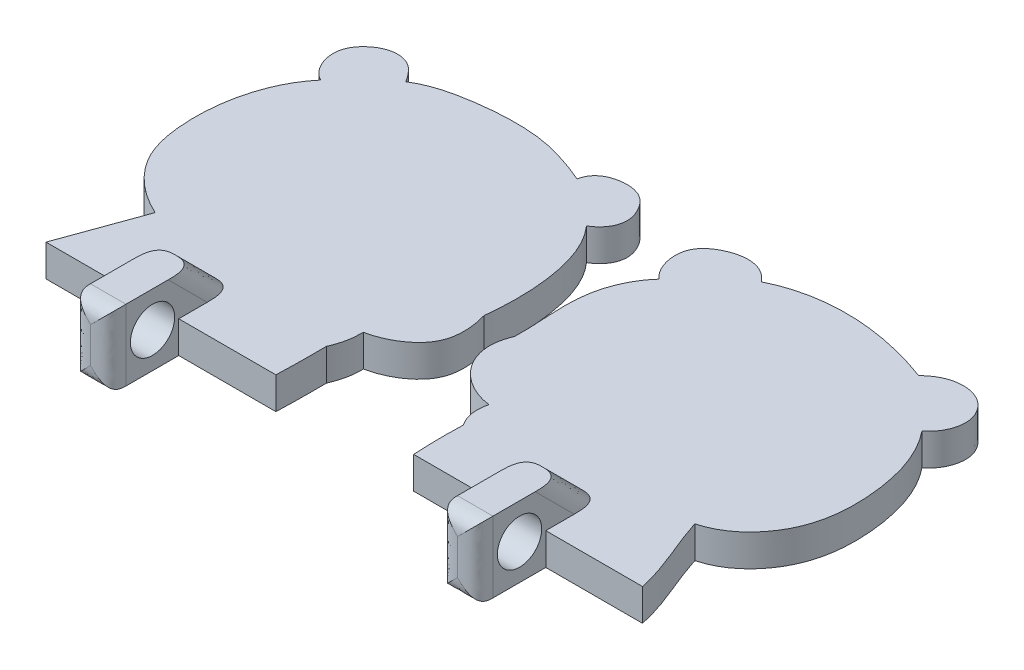
SolidWorks part; units mm, degrees
ref_plane "前视基准面" through (0, 0, 0) normal (0, 0, 1) x (1, 0, 0)
ref_plane "上视基准面" through (0, 0, 0) normal (0, 1, 0) x (1, 0, 0)
ref_plane "右视基准面" through (0, 0, 0) normal (1, 0, 0) x (0, 0, -1)
other "Configuration Table"
sketch "草图1" plane through (0, 0, 0) normal (0, 1, 0) x (1, 0, 0)
  line L0 (-15.2017, -5.0806) -> (-16.8357, -9.594)
  line L1 (-16.8357, -9.594) -> (-3.9124, -9.594)
  line L2 (3.9008, -9.594) -> (16.772, -9.594)
  arc A0 (-3.9124, -9.594) -> (-3.8798, -6.789) centre (-62.9106, -7.507) ccw
  arc A1 (3.8716, -6.7805) -> (3.9008, -9.594) centre (33.2778, -7.8816) ccw
  spline S0 degree 3 poles (-3.8798, -6.789) (-3.7551, -6.5149) (-3.6624, -6.2324) (-3.5439, -5.6496) (-3.5185, -5.3474) (-3.5264, -5.0463) knots 0 0 0 0 0.5 0.5 1 1 1 1
  spline S1 degree 3 poles (-3.5264, -5.0463) (-3.4096, -5.0216) (-3.293, -4.9962) (-3.0649, -4.9318) (-2.9527, -4.8947) (-2.6213, -4.7699) (-2.4069, -4.6691) (-1.9927, -4.4291) (-1.7979, -4.2927) (-1.4398, -3.9816) (-1.2745, -3.804) (-1.0721, -3.5109) (-1.0118, -3.4086) (-0.9084, -3.1927) (-0.8661, -3.0795) (-0.7674, -2.7366) (-0.7363, -2.4972) (-0.7177, -1.7829) (-0.8001, -1.3114) (-0.9363, -0.8529) knots 0 0 0 0 0.0625 0.0625 0.125 0.125 0.25 0.25 0.375 0.375 0.5 0.5 0.5625 0.5625 0.625 0.625 0.75 0.75 1 1 1 1
  spline S2 degree 3 poles (-0.9363, -0.8529) (-0.8688, -0.2177) (-0.831, 0.419) (-0.84, 1.6967) (-0.8861, 2.3328) (-1.0823, 3.5953) (-1.2282, 4.2135) (-1.5728, 5.0952) (-1.7089, 5.3818) (-1.9554, 5.7972) (-2.0441, 5.9322) (-2.2339, 6.1918) (-2.3373, 6.3153) (-2.4414, 6.4384) knots 0 0 0 0 0.25 0.25 0.5 0.5 0.75 0.75 0.875 0.875 0.9375 0.9375 1 1 1 1
  spline S3 degree 3 poles (-2.4414, 6.4384) (-2.3818, 6.4743) (-2.3211, 6.5091) (-2.2059, 6.5859) (-2.1512, 6.6279) (-1.9952, 6.7635) (-1.9006, 6.8682) (-1.7392, 7.0963) (-1.6726, 7.2184) (-1.5729, 7.4815) (-1.5418, 7.6177) (-1.5205, 8.0385) (-1.6007, 8.3173) (-1.8447, 8.8161) (-2.009, 9.05) (-2.3319, 9.3186) (-2.4525, 9.3916) (-2.7083, 9.498) (-2.8459, 9.5337) (-3.2581, 9.594) (-3.5421, 9.5773) (-4.0832, 9.4529) (-4.3492, 9.3391) (-4.6639, 9.061) (-4.7529, 8.9507) (-4.8514, 8.7657) (-4.8783, 8.7015) (-4.9207, 8.5686) (-4.9362, 8.4998) (-4.9536, 8.4318) knots 0 0 0 0 0.03125 0.03125 0.0625 0.0625 0.125 0.125 0.1875 0.1875 0.25 0.25 0.375 0.375 0.5 0.5 0.5625 0.5625 0.625 0.625 0.75 0.75 0.875 0.875 0.9375 0.9375 0.96875 0.96875 1 1 1 1
  spline S4 degree 3 poles (-4.9536, 8.4318) (-5.3352, 8.591) (-5.718, 8.7447) (-6.4926, 9.0136) (-6.8839, 9.1307) (-7.6784, 9.3135) (-8.0821, 9.377) (-8.9026, 9.4476) (-9.3213, 9.4565) (-10.57, 9.4267) (-11.3934, 9.3365) (-12.6165, 9.111) (-13.0245, 9.0165) (-13.7182, 8.782) (-14.006, 8.6602) (-14.3721, 8.4588) (-14.4616, 8.4041) (-14.5512, 8.3495) knots 0 0 0 0 0.125 0.125 0.25 0.25 0.375 0.375 0.5 0.5 0.75 0.75 0.875 0.875 0.96875 0.96875 1 1 1 1
  spline S5 degree 3 poles (-14.5512, 8.3495) (-14.7099, 8.5872) (-14.8725, 8.8243) (-15.1787, 9.125) (-15.289, 9.2148) (-15.5375, 9.3594) (-15.6711, 9.4089) (-16.0879, 9.4966) (-16.3857, 9.4747) (-16.789, 9.3383) (-16.9191, 9.2755) (-17.1611, 9.1263) (-17.2735, 9.0405) (-17.483, 8.8488) (-17.58, 8.7419) (-17.7458, 8.5119) (-17.8165, 8.3858) (-17.918, 8.1202) (-17.9477, 7.9825) (-17.9702, 7.6983) (-17.9627, 7.555) (-17.917, 7.2757) (-17.8782, 7.1367) (-17.7738, 6.8727) (-17.7086, 6.747) (-17.5497, 6.5092) (-17.4579, 6.4002) (-17.3011, 6.2563) (-17.2451, 6.2113) (-17.127, 6.1299) (-17.0649, 6.094) (-17.0038, 6.0565) knots 0 0 0 0 0.125 0.125 0.1875 0.1875 0.25 0.25 0.375 0.375 0.4375 0.4375 0.5 0.5 0.5625 0.5625 0.625 0.625 0.6875 0.6875 0.75 0.75 0.8125 0.8125 0.875 0.875 0.9375 0.9375 0.96875 0.96875 1 1 1 1
  spline S6 degree 3 poles (-17.0038, 6.0565) (-17.0904, 5.9511) (-17.1771, 5.8457) (-17.3396, 5.6289) (-17.4168, 5.5182) (-17.6374, 5.18) (-17.7695, 4.9461) (-18.1259, 4.2219) (-18.3111, 3.7037) (-18.5814, 2.6579) (-18.67, 2.1274) (-18.7634, 1.0528) (-18.7665, 0.5051) (-18.6882, -0.5747) (-18.6111, -1.1117) (-18.3772, -1.8972) (-18.2807, -2.15) (-18.0417, -2.6333) (-17.9, -2.8644) (-17.4154, -3.5276) (-17.0312, -3.9096) (-16.3838, -4.4125) (-16.1588, -4.5656) (-15.8092, -4.7743) (-15.6906, -4.8404) (-15.4491, -4.9655) (-15.3256, -5.0233) (-15.2017, -5.0806) knots 0 0 0 0 0.03125 0.03125 0.0625 0.0625 0.125 0.125 0.25 0.25 0.375 0.375 0.5 0.5 0.625 0.625 0.6875 0.6875 0.75 0.75 0.875 0.875 0.9375 0.9375 0.96875 0.96875 1 1 1 1
  spline S7 degree 3 poles (16.772, -9.594) (16.6107, -8.8081) (16.3306, -8.0546) (15.8849, -6.9382) (15.6553, -6.3825) (15.4419, -5.8208) (15.3061, -5.4438) (15.2428, -5.2536) (15.181, -5.0628) knots 0 0 0 0 0.5 0.5 0.75 0.875 0.875 1 1 1 1
  spline S8 degree 3 poles (15.181, -5.0628) (15.311, -5.0248) (15.4407, -4.9863) (15.6926, -4.8933) (15.8157, -4.8408) (16.1766, -4.6659) (16.4072, -4.5256) (16.8433, -4.2028) (17.044, -4.0243) (17.4149, -3.6366) (17.5859, -3.4263) (17.8941, -2.9815) (18.03, -2.7497) (18.2671, -2.2682) (18.3687, -2.0172) (18.6173, -1.2445) (18.7065, -0.7175) (18.7615, 0.0852) (18.7665, 0.356) (18.7543, 0.8938) (18.7374, 1.1608) (18.661, 1.9575) (18.5764, 2.4829) (18.3815, 3.2595) (18.3052, 3.5165) (18.1254, 4.0258) (18.0223, 4.2769) (17.7908, 4.7615) (17.5977, 5.1138) (17.373, 5.4482) (17.2159, 5.6669) (17.1324, 5.7736) (17.0487, 5.88) knots 0 0 0 0 0.03125 0.03125 0.0625 0.0625 0.125 0.125 0.1875 0.1875 0.25 0.25 0.3125 0.3125 0.375 0.375 0.5 0.5 0.5625 0.5625 0.625 0.625 0.75 0.75 0.8125 0.8125 0.875 0.875 0.9375 0.96875 0.96875 1 1 1 1
  spline S9 degree 3 poles (17.0487, 5.88) (17.1033, 5.9233) (17.1589, 5.9657) (17.2629, 6.0572) (17.312, 6.1058) (17.4511, 6.2591) (17.5339, 6.3727) (17.6748, 6.6136) (17.7324, 6.7394) (17.8225, 7.0011) (17.8552, 7.139) (17.8895, 7.4144) (17.8918, 7.5524) (17.8621, 7.829) (17.8288, 7.9671) (17.7292, 8.2254) (17.6624, 8.3496) (17.5022, 8.5785) (17.4099, 8.6824) (17.1998, 8.8684) (17.0843, 8.9473) (16.8386, 9.0765) (16.7065, 9.1277) (16.3037, 9.2372) (16.0192, 9.2535) (15.6062, 9.199) (15.4685, 9.1675) (15.2038, 9.0821) (15.076, 9.0282) (14.8295, 8.8987) (14.7108, 8.8227) (14.5456, 8.6955) (14.4925, 8.6508) (14.3902, 8.5566) (14.3416, 8.5063) (14.293, 8.4561) knots 0 0 0 0 0.03125 0.03125 0.0625 0.0625 0.125 0.125 0.1875 0.1875 0.25 0.25 0.3125 0.3125 0.375 0.375 0.4375 0.4375 0.5 0.5 0.5625 0.5625 0.625 0.625 0.75 0.75 0.8125 0.8125 0.875 0.875 0.9375 0.9375 0.96875 0.96875 1 1 1 1
  spline S10 degree 3 poles (14.293, 8.4561) (13.9286, 8.5923) (13.5617, 8.7193) (12.8193, 8.9447) (12.4443, 9.0446) (11.6861, 9.216) (11.3036, 9.2873) (10.5398, 9.3962) (10.1574, 9.4343) (9.0085, 9.4929) (8.2402, 9.4595) (7.0832, 9.2553) (6.7055, 9.1626) (6.1522, 8.9833) (5.9699, 8.9168) (5.61, 8.7697) (5.433, 8.6873) (5.257, 8.6016) knots 0 0 0 0 0.125 0.125 0.25 0.25 0.375 0.375 0.5 0.5 0.75 0.75 0.875 0.875 0.9375 0.9375 1 1 1 1
  spline S11 degree 3 poles (5.257, 8.6016) (5.2116, 8.6551) (5.1666, 8.7091) (5.0708, 8.8106) (5.0206, 8.8588) (4.8623, 8.995) (4.7449, 9.0756) (4.3711, 9.2683) (4.0899, 9.3312) (3.6698, 9.3335) (3.5281, 9.3195) (3.2535, 9.2688) (3.1192, 9.2321) (2.8554, 9.1401) (2.7251, 9.0846) (2.4762, 8.958) (2.357, 8.8866) (2.0196, 8.6411) (1.8175, 8.4313) (1.5791, 7.9174) (1.5434, 7.6303) (1.5707, 7.2118) (1.5937, 7.0716) (1.6637, 6.7993) (1.7103, 6.6674) (1.8277, 6.4122) (1.8988, 6.2888) (2.0224, 6.1201) (2.0667, 6.0662) (2.1621, 5.964) (2.2142, 5.9165) (2.2653, 5.8681) knots 0 0 0 0 0.03125 0.03125 0.0625 0.0625 0.125 0.125 0.25 0.25 0.3125 0.3125 0.375 0.375 0.4375 0.4375 0.5 0.5 0.625 0.625 0.75 0.75 0.8125 0.8125 0.875 0.875 0.9375 0.9375 0.96875 0.96875 1 1 1 1
  spline S12 degree 3 poles (2.2653, 5.8681) (2.166, 5.7544) (2.068, 5.64) (1.8882, 5.4011) (1.8044, 5.2779) (1.5697, 4.8981) (1.4357, 4.631) (1.21, 4.0709) (1.121, 3.7841) (0.9888, 3.2019) (0.9466, 2.9056) (0.8773, 2.0042) (0.905, 1.4019) (0.9707, 0.2003) (1.0084, -0.4004) (0.989, -1.0022) knots 0 0 0 0 0.0625 0.0625 0.125 0.125 0.25 0.25 0.375 0.375 0.5 0.5 0.75 0.75 1 1 1 1
  spline S13 degree 3 poles (0.989, -1.0022) (0.8977, -1.2195) (0.8273, -1.442) (0.7422, -1.901) (0.7269, -2.1394) (0.766, -2.6038) (0.8204, -2.8361) (0.9857, -3.2738) (1.0972, -3.4819) (1.3693, -3.8654) (1.5266, -4.0381) (1.8785, -4.35) (2.0705, -4.4865) (2.4756, -4.7187) (2.6922, -4.816) (3.0252, -4.927) (3.1377, -4.9583) (3.3659, -5.0091) (3.4822, -5.0264) (3.5983, -5.044) knots 0 0 0 0 0.125 0.125 0.25 0.25 0.375 0.375 0.5 0.5 0.625 0.625 0.75 0.75 0.875 0.875 0.9375 0.9375 1 1 1 1
  spline S14 degree 3 poles (3.5983, -5.044) (3.5612, -5.1916) (3.5362, -5.3403) (3.5157, -5.6406) (3.5208, -5.7942) (3.5654, -6.0927) (3.6045, -6.2373) (3.7152, -6.5176) (3.7873, -6.6534) (3.8716, -6.7805) knots 0 0 0 0 0.25 0.25 0.5 0.5 0.75 0.75 1 1 1 1
extrude "凸台-拉伸1" add sketch "草图1" along normal blind 1.8
sketch "草图2" plane through (0, 0, 9.594) normal (0, 0, 1) x (1, 0, 0)
  line L0 (-10.374, 1.8) -> (-10.374, 0) construction
  line L1 (-16.8357, 1.8) -> (-3.9124, 1.8) construction
  line L2 (-16.8357, 0) -> (-3.9124, 0) construction
  line L3 (10.3364, 1.8) -> (10.3364, 0) construction
  line L4 (3.9008, 1.8) -> (16.772, 1.8) construction
  line L5 (3.9008, 0) -> (16.772, 0) construction
  line L7 (-11.374, 4) -> (-9.374, 4)
  line L8 (-11.374, 4) -> (-11.374, 0)
  line L9 (-11.374, 0) -> (-9.374, 0)
  line L10 (-9.374, 4) -> (-9.374, 0)
  line L11 (-11.374, 4) -> (-9.374, 0) construction
  line L12 (-11.374, 0) -> (-9.374, 4) construction
  line L13 (9.3364, 4) -> (11.3364, 4)
  line L14 (9.3364, 4) -> (9.3364, 0)
  line L15 (9.3364, 0) -> (11.3364, 0)
  line L16 (11.3364, 4) -> (11.3364, 0)
  line L17 (9.3364, 4) -> (11.3364, 0) construction
  line L18 (9.3364, 0) -> (11.3364, 4) construction
  point P12 (-10.374, 2)
  point P17 (10.3364, 2)
  dimension "D1" = 2
  dimension "D2" = 2
  dimension "D3" = 4
  dimension "D4" = 4
extrude "凸台-拉伸2" add sketch "草图2" along normal blind 4
chamfer "倒角1" distance 3 angle 45 1 edges at (-10.374, 1.8, 9.594)
chamfer "倒角2" distance 3 angle 45 1 edges
fillet "圆角2" radius 1 4 edges at (-10.374, 0, 13.594) (-11.374, 2, 13.594) (-10.374, 4, 13.594) (-9.374, 2, 13.594) curvature continuous yes
fillet "圆角3" radius 1 4 edges at (10.3364, 0, 13.594) (9.3364, 2, 13.594) (10.3364, 4, 13.594) (11.3364, 2, 13.594) curvature continuous yes
sketch "草图3" plane through (11.3364, 0, 0) normal (1, 0, 0) x (0, 0, -1)
  line L0 (-13.594, 3) -> (-13.594, 1) construction
  circle A0 centre (-11.094, 2) radius 1.25
  dimension "D1" = 2.5
  dimension "D2" = 2.5
extrude "切除-拉伸1" cut sketch "草图3" against normal blind 28
fillet "圆角4" radius 1 2 edges at (-11.374, 2.9, 7.694) (-9.374, 2.9, 7.694) curvature continuous yes
fillet "圆角5" radius 1 2 edges at (11.3364, 2.9, 7.694) (9.3364, 2.9, 7.694) curvature continuous yes
sketch "草图4" plane through (0, 1.8, 0) normal (0, 1, 0) x (1, 0, 0)
  line L10 (-9.394, -8.0082) -> (-9.394, -9.614)
  line L11 (-9.394, -9.614) -> (-3.8931, -9.614)
  line L12 (-15.2268, -5.0911) -> (-16.8642, -9.614)
  line L13 (-16.8642, -9.614) -> (-11.354, -9.614)
  line L14 (-11.354, -9.614) -> (-11.354, -8.0082)
  line L15 (-9.394, -8.0082) -> (-9.394, -9.614)
  line L16 (-9.394, -9.614) -> (-3.8931, -9.614)
  line L17 (-15.2268, -5.0911) -> (-16.8642, -9.614)
  line L18 (-16.8642, -9.614) -> (-11.354, -9.614)
  line L19 (-11.354, -9.614) -> (-11.354, -8.0082)
  line L31 (9.3564, -9.614) -> (9.3564, -8.0082)
  line L32 (11.3164, -8.0082) -> (11.3164, -9.614)
  line L33 (11.3164, -9.614) -> (16.7965, -9.614)
  line L34 (3.882, -9.614) -> (9.3564, -9.614)
  line L35 (9.3564, -9.614) -> (9.3564, -8.0082)
  line L36 (11.3164, -8.0082) -> (11.3164, -9.614)
  line L37 (11.3164, -9.614) -> (16.7965, -9.614)
  line L38 (3.882, -9.614) -> (9.3564, -9.614)
  arc A2 (-3.8931, -9.614) -> (-3.8598, -6.7932) centre (-62.9106, -7.507) ccw
  arc A3 (-3.8931, -9.614) -> (-3.8598, -6.7932) centre (-62.9106, -7.507) ccw
  arc A7 (3.8513, -6.7862) -> (3.882, -9.614) centre (33.2778, -7.8816) ccw
  arc A8 (3.8513, -6.7862) -> (3.882, -9.614) centre (33.2778, -7.8816) ccw
  spline S18 degree 3 poles (-4008.6204, 131.2602) (58.4278, -31.6233) (-12.5627, -18.0279) (-11.314, -7.3478) (-11.2802, -7.1868) (-11.172, -6.9611) (-11.126, -6.8916) (-11.0086, -6.7718) (-10.94, -6.7248) (-10.7873, -6.6564) (-10.7056, -6.6392) (-1.7946, -5.4737) (12.6768, -85.8409) (-260.2207, 3985.3377) knots -15.710344 -15.710344 -15.710344 -15.710344 0.25 0.25 0.5 0.5 0.625 0.625 0.75 0.75 0.875 0.875 14.238448 14.238448 14.238448 14.238448 only from (-11.354, -8.0082) to (-10.374, -6.614)
  spline S19 degree 3 poles (349.7456, 3977.0103) (-35.796, -86.154) (-18.9879, -5.4734) (-10.0434, -6.6391) (-9.9605, -6.6566) (-9.8096, -6.724) (-9.7395, -6.7721) (-9.6235, -6.89) (-9.5766, -6.9605) (-9.5049, -7.1093) (-9.4783, -7.189) (-9.4383, -7.349) (-9.4245, -7.4301) (-8.1919, -17.9509) (-78.1632, -39.99) (3887.6311, 892.6218) knots -13.345557 -13.345557 -13.345557 -13.345557 0.125 0.125 0.25 0.25 0.375 0.375 0.5 0.5 0.625 0.625 0.75 0.75 16.684036 16.684036 16.684036 16.684036 only from (-10.374, -6.614) to (-9.394, -8.0082)
  spline S20 degree 3 poles (2048.1962, 3417.2726) (-279.9253, 4.3116) (-8.851, -31.7824) (3.7238, 29.8984) (-508.6231, 119.4535) (3508.0427, -1916.1775) knots -43.795404 -43.795404 -43.795404 -43.795404 0.5 0.5 61.956812 61.956812 61.956812 61.956812 only from (-3.8598, -6.7932) to (-3.5061, -5.0624)
  spline S21 degree 3 poles (1402.5526, -3749.3123) (-44.3506, 42.8584) (-13.4245, -7.9218) (-3.044, -4.9461) (-2.9317, -4.9085) (-2.6001, -4.7825) (-2.3858, -4.6808) (-1.9718, -4.4392) (-1.7766, -4.3016) (-1.4187, -3.9886) (-1.2536, -3.8101) (-1.0516, -3.5159) (-0.9915, -3.4131) (-0.8885, -3.1968) (-0.8462, -3.0831) (-0.7476, -2.7392) (-0.7164, -2.4994) (-0.1016, 20.792) (-220.4088, 31.6025) (3920.243, -790.6913) knots -5.55998 -5.55998 -5.55998 -5.55998 0.0625 0.0625 0.125 0.125 0.25 0.25 0.375 0.375 0.5 0.5 0.5625 0.5625 0.625 0.625 0.75 0.75 12.818632 12.818632 12.818632 12.818632 only from (-3.5061, -5.0624) to (-0.916, -0.8511)
  spline S22 degree 3 poles (3988.1598, -267.3402) (-221.4527, -84.2761) (-0.4929, -45.2055) (-0.82, 1.6941) (-0.8663, 2.3328) (-1.0116, 3.272) (-1.0718, 3.5828) (-1.2261, 4.1982) (-1.3206, 4.5039) (-1.5533, 5.1013) (-1.7583, 5.5316) (-2.0183, 5.9296) (-9.3815, 16.0894) (-71.3063, -5.9039) (3429.5649, 2059.6702) knots -17.900046 -17.900046 -17.900046 -17.900046 0.25 0.25 0.5 0.5 0.625 0.625 0.75 0.75 0.875 0.9375 0.9375 5.80626 5.80626 5.80626 5.80626 only from (-0.916, -0.8511) to (-2.411, 6.4333)
  spline S23 degree 3 poles (2580.0375, -3047.8614) (-38.8422, 30.7106) (-7.2695, 3.0777) (-2.1757, 6.5834) (-2.1214, 6.6263) (-1.9667, 6.7643) (-1.8731, 6.8702) (-1.7131, 7.1011) (-1.6475, 7.2244) (-1.5501, 7.489) (-1.5202, 7.6268) (-1.5023, 8.0484) (-1.5836, 8.3289) (-1.8294, 8.8294) (-1.9951, 9.0642) (-2.3183, 9.3335) (-2.4405, 9.4077) (-2.6975, 9.5155) (-2.8356, 9.5519) (-3.2504, 9.614) (-3.5357, 9.5982) (-4.08, 9.4752) (-4.3461, 9.364) (-4.6679, 9.0862) (-4.758, 8.9779) (-4.8611, 8.7924) (-4.8892, 8.7283) (-6.7343, 3.2877) (33.0143, -17.3237) (-3766.1994, 1369.1606) knots -2.718898 -2.718898 -2.718898 -2.718898 0.03125 0.03125 0.0625 0.0625 0.125 0.125 0.1875 0.1875 0.25 0.25 0.375 0.375 0.5 0.5 0.5625 0.5625 0.625 0.625 0.75 0.75 0.875 0.875 0.9375 0.9375 0.96875 0.96875 3.505852 3.505852 3.505852 3.505852 only from (-2.411, 6.4333) to (-4.9673, 8.4592)
  spline S24 degree 3 poles (984.5291, 3883.2745) (25.6123, -97.2483) (20.0432, -0.1362) (-6.5035, 9.0379) (-6.8942, 9.1542) (-7.6876, 9.3355) (-8.0907, 9.3983) (-8.9102, 9.4678) (-9.3284, 9.4765) (-10.5733, 9.4463) (-11.3945, 9.3564) (-12.4117, 9.1692) (-12.6145, 9.1271) (-13.0184, 9.0282) (-13.2202, 8.9711) (-13.7138, 8.8051) (-14.0008, 8.6845) (-23.1709, 3.6852) (-13.9017, -42.435) (-1653.1802, 3656.8635) knots -8.332667 -8.332667 -8.332667 -8.332667 0.125 0.125 0.25 0.25 0.375 0.375 0.5 0.5 0.75 0.75 0.8125 0.8125 0.875 0.875 0.96875 0.96875 4.010213 4.010213 4.010213 4.010213 only from (-4.9673, 8.4592) to (-14.5452, 8.3766)
  spline S25 degree 3 poles (3027.7667, 2604.9155) (-79.7425, -77.3097) (-6.026, 0.2949) (-15.1784, 9.1511) (-15.29, 9.2402) (-15.5402, 9.3823) (-15.676, 9.4313) (-16.0954, 9.5166) (-16.3944, 9.4935) (-16.7993, 9.3556) (-16.9297, 9.2926) (-17.1731, 9.1424) (-17.2859, 9.0561) (-17.6013, 8.7678) (-17.7803, 8.5332) (-17.9355, 8.1324) (-17.966, 7.9941) (-17.9902, 7.7093) (-17.9836, 7.5649) (-17.9395, 7.2841) (-17.9015, 7.1444) (-17.7986, 6.8782) (-17.734, 6.7515) (-17.5769, 6.5119) (-17.4855, 6.4009) (-17.3301, 6.2548) (-17.2751, 6.2092) (-12.2769, 2.6495) (16.3329, 35.4248) (-2201.1269, -3344.8238) knots -5.344029 -5.344029 -5.344029 -5.344029 0.125 0.125 0.1875 0.1875 0.25 0.25 0.375 0.375 0.4375 0.4375 0.5 0.5 0.625 0.625 0.6875 0.6875 0.75 0.75 0.8125 0.8125 0.875 0.875 0.9375 0.9375 0.96875 0.96875 3.595855 3.595855 3.595855 3.595855 only from (-14.5452, 8.3766) to (-17.0339, 6.0514)
  spline S26 degree 3 poles (-3489.7471, 1990.2985) (41.2907, 0.8501) (-9.9636, 15.5797) (-17.3683, 5.623) (-17.4452, 5.5121) (-17.6646, 5.1732) (-17.7961, 4.9389) (-18.1505, 4.2139) (-18.3347, 3.6954) (-18.6033, 2.65) (-18.6913, 2.1196) (-18.7836, 1.0453) (-18.7863, 0.4977) (-18.7075, -0.5813) (-18.6301, -1.118) (-18.3963, -1.9032) (-18.2998, -2.1559) (-18.0613, -2.6392) (-17.92, -2.8702) (-17.4364, -3.534) (-17.0532, -3.9165) (-16.4072, -4.4203) (-16.1824, -4.574) (-15.8334, -4.7835) (-15.715, -4.8499) (-3.8347, -11.0434) (34.4582, 27.3081) (-2030.3323, -3460.1012) knots -2.800569 -2.800569 -2.800569 -2.800569 0.03125 0.03125 0.0625 0.0625 0.125 0.125 0.25 0.25 0.375 0.375 0.5 0.5 0.625 0.625 0.6875 0.6875 0.75 0.75 0.875 0.875 0.9375 0.9375 0.96875 0.96875 4.017807 4.017807 4.017807 4.017807 only from (-17.0339, 6.0514) to (-15.2268, -5.0911)
  spline S27 degree 3 poles (-11.354, -8.0082) (-11.354, -7.8426) (-11.3525, -7.6772) (-11.314, -7.3478) (-11.2802, -7.1868) (-11.172, -6.9611) (-11.126, -6.8916) (-11.0086, -6.7718) (-10.94, -6.7248) (-10.7873, -6.6564) (-10.7056, -6.6392) (-10.5404, -6.6176) (-10.4574, -6.614) (-10.374, -6.614) knots 0 0 0 0 0.25 0.25 0.5 0.5 0.625 0.625 0.75 0.75 0.875 0.875 1 1 1 1
  spline S28 degree 3 poles (-10.374, -6.614) (-10.2908, -6.614) (-10.2078, -6.6176) (-10.0434, -6.6391) (-9.9605, -6.6566) (-9.8096, -6.724) (-9.7395, -6.7721) (-9.6235, -6.89) (-9.5766, -6.9605) (-9.5049, -7.1093) (-9.4783, -7.189) (-9.4383, -7.349) (-9.4245, -7.4301) (-9.3957, -7.6758) (-9.394, -7.8424) (-9.394, -8.0082) knots 0 0 0 0 0.125 0.125 0.25 0.25 0.375 0.375 0.5 0.5 0.625 0.625 0.75 0.75 1 1 1 1
  spline S29 degree 3 poles (-3.8598, -6.7932) (-3.7367, -6.5221) (-3.6434, -6.2384) (-3.5245, -5.6551) (-3.4994, -5.36) (-3.5061, -5.0624) knots 0 0 0 0 0.5 0.5 1 1 1 1
  spline S30 degree 3 poles (-3.5061, -5.0624) (-3.3889, -5.0376) (-3.2722, -5.0115) (-3.044, -4.9461) (-2.9317, -4.9085) (-2.6001, -4.7825) (-2.3858, -4.6808) (-1.9718, -4.4392) (-1.7766, -4.3016) (-1.4187, -3.9886) (-1.2536, -3.8101) (-1.0516, -3.5159) (-0.9915, -3.4131) (-0.8885, -3.1968) (-0.8462, -3.0831) (-0.7476, -2.7392) (-0.7164, -2.4994) (-0.6975, -1.7831) (-0.7797, -1.3108) (-0.916, -0.8511) knots 0 0 0 0 0.0625 0.0625 0.125 0.125 0.25 0.25 0.375 0.375 0.5 0.5 0.5625 0.5625 0.625 0.625 0.75 0.75 1 1 1 1
  spline S31 degree 3 poles (-0.916, -0.8511) (-0.8486, -0.2162) (-0.8111, 0.4197) (-0.82, 1.6941) (-0.8663, 2.3328) (-1.0116, 3.272) (-1.0718, 3.5828) (-1.2261, 4.1982) (-1.3206, 4.5039) (-1.5533, 5.1013) (-1.7583, 5.5316) (-2.0183, 5.9296) (-2.2049, 6.1871) (-2.3073, 6.3106) (-2.411, 6.4333) knots 0 0 0 0 0.25 0.25 0.5 0.5 0.625 0.625 0.75 0.75 0.875 0.9375 0.9375 1 1 1 1
  spline S32 degree 3 poles (-2.411, 6.4333) (-2.3508, 6.4693) (-2.2901, 6.5046) (-2.1757, 6.5834) (-2.1214, 6.6263) (-1.9667, 6.7643) (-1.8731, 6.8702) (-1.7131, 7.1011) (-1.6475, 7.2244) (-1.5501, 7.489) (-1.5202, 7.6268) (-1.5023, 8.0484) (-1.5836, 8.3289) (-1.8294, 8.8294) (-1.9951, 9.0642) (-2.3183, 9.3335) (-2.4405, 9.4077) (-2.6975, 9.5155) (-2.8356, 9.5519) (-3.2504, 9.614) (-3.5357, 9.5982) (-4.08, 9.4752) (-4.3461, 9.364) (-4.6679, 9.0862) (-4.758, 8.9779) (-4.8611, 8.7924) (-4.8892, 8.7283) (-4.9341, 8.5959) (-4.9502, 8.5274) (-4.9673, 8.4592) knots 0 0 0 0 0.03125 0.03125 0.0625 0.0625 0.125 0.125 0.1875 0.1875 0.25 0.25 0.375 0.375 0.5 0.5 0.5625 0.5625 0.625 0.625 0.75 0.75 0.875 0.875 0.9375 0.9375 0.96875 0.96875 1 1 1 1
  spline S33 degree 3 poles (-4.9673, 8.4592) (-5.3481, 8.6178) (-5.7302, 8.7707) (-6.5035, 9.0379) (-6.8942, 9.1542) (-7.6876, 9.3355) (-8.0907, 9.3983) (-8.9102, 9.4678) (-9.3284, 9.4765) (-10.5733, 9.4463) (-11.3945, 9.3564) (-12.4117, 9.1692) (-12.6145, 9.1271) (-13.0184, 9.0282) (-13.2202, 8.9711) (-13.7138, 8.8051) (-14.0008, 8.6845) (-14.3664, 8.4852) (-14.4559, 8.431) (-14.5452, 8.3766) knots 0 0 0 0 0.125 0.125 0.25 0.25 0.375 0.375 0.5 0.5 0.75 0.75 0.8125 0.8125 0.875 0.875 0.96875 0.96875 1 1 1 1
  spline S34 degree 3 poles (-14.5452, 8.3766) (-14.7046, 8.6148) (-14.8681, 8.8509) (-15.1784, 9.1511) (-15.29, 9.2402) (-15.5402, 9.3823) (-15.676, 9.4313) (-16.0954, 9.5166) (-16.3944, 9.4935) (-16.7993, 9.3556) (-16.9297, 9.2926) (-17.1731, 9.1424) (-17.2859, 9.0561) (-17.6013, 8.7678) (-17.7803, 8.5332) (-17.9355, 8.1324) (-17.966, 7.9941) (-17.9902, 7.7093) (-17.9836, 7.5649) (-17.9395, 7.2841) (-17.9015, 7.1444) (-17.7986, 6.8782) (-17.734, 6.7515) (-17.5769, 6.5119) (-17.4855, 6.4009) (-17.3301, 6.2548) (-17.2751, 6.2092) (-17.1576, 6.1255) (-17.0955, 6.0888) (-17.0339, 6.0514) knots 0 0 0 0 0.125 0.125 0.1875 0.1875 0.25 0.25 0.375 0.375 0.4375 0.4375 0.5 0.5 0.625 0.625 0.6875 0.6875 0.75 0.75 0.8125 0.8125 0.875 0.875 0.9375 0.9375 0.96875 0.96875 1 1 1 1
  spline S35 degree 3 poles (-17.0339, 6.0514) (-17.1205, 5.946) (-17.2067, 5.8403) (-17.3683, 5.623) (-17.4452, 5.5121) (-17.6646, 5.1732) (-17.7961, 4.9389) (-18.1505, 4.2139) (-18.3347, 3.6954) (-18.6033, 2.65) (-18.6913, 2.1196) (-18.7836, 1.0453) (-18.7863, 0.4977) (-18.7075, -0.5813) (-18.6301, -1.118) (-18.3963, -1.9032) (-18.2998, -2.1559) (-18.0613, -2.6392) (-17.92, -2.8702) (-17.4364, -3.534) (-17.0532, -3.9165) (-16.4072, -4.4203) (-16.1824, -4.574) (-15.8334, -4.7835) (-15.715, -4.8499) (-15.4739, -4.9756) (-15.3506, -5.0337) (-15.2268, -5.0911) knots 0 0 0 0 0.03125 0.03125 0.0625 0.0625 0.125 0.125 0.25 0.25 0.375 0.375 0.5 0.5 0.625 0.625 0.6875 0.6875 0.75 0.75 0.875 0.875 0.9375 0.9375 0.96875 0.96875 1 1 1 1
  spline S57 degree 3 poles (-3987.91, 131.2602) (79.1382, -31.6233) (8.1477, -18.0279) (9.3965, -7.3478) (9.4303, -7.1868) (9.5385, -6.9611) (9.5845, -6.8916) (9.7019, -6.7718) (9.7704, -6.7248) (9.9232, -6.6564) (10.0049, -6.6392) (18.9159, -5.4737) (33.3873, -85.8409) (-239.5103, 3985.3377) knots -15.710344 -15.710344 -15.710344 -15.710344 0.25 0.25 0.5 0.5 0.625 0.625 0.75 0.75 0.875 0.875 14.238448 14.238448 14.238448 14.238448 only from (9.3564, -8.0082) to (10.3364, -6.614)
  spline S58 degree 3 poles (370.4561, 3977.0103) (-15.0855, -86.154) (1.7226, -5.4734) (10.6671, -6.6391) (10.7499, -6.6566) (10.9009, -6.724) (10.971, -6.7721) (11.087, -6.89) (11.1339, -6.9605) (11.2056, -7.1093) (11.2322, -7.189) (11.2722, -7.349) (11.286, -7.4301) (12.5186, -17.9509) (-57.4527, -39.99) (3908.3415, 892.6218) knots -13.345557 -13.345557 -13.345557 -13.345557 0.125 0.125 0.25 0.25 0.375 0.375 0.5 0.5 0.625 0.625 0.75 0.75 16.684036 16.684036 16.684036 16.684036 only from (10.3364, -6.614) to (11.3164, -8.0082)
  spline S59 degree 3 poles (-3817.4946, -1145.9221) (-65.9039, -92.0939) (25.8259, -36.4899) (16.3537, -8.0734) (16.2099, -7.6989) (15.9128, -6.9535) (15.6828, -6.3972) (15.4685, -5.8349) (7.7259, 15.5757) (57.0662, 58.4566) (-3746.6658, -1362.3831) knots -18.159221 -18.159221 -18.159221 -18.159221 0.25 0.25 0.5 0.5 0.75 0.875 0.875 14.936753 14.936753 14.936753 14.936753 only from (16.7965, -9.614) to (15.2064, -5.0762)
  spline S60 degree 3 poles (1713.003, -3626.6508) (-30.3086, 40.4531) (5.3468, -8.7913) (15.7173, -4.9048) (15.8402, -4.8517) (16.2005, -4.6753) (16.4307, -4.5341) (16.8656, -4.2101) (17.0659, -4.0311) (17.4361, -3.6426) (17.6069, -3.4318) (17.9143, -2.9868) (18.0499, -2.7549) (18.2867, -2.2733) (18.3881, -2.0222) (18.6366, -1.2494) (18.7265, -0.7202) (18.8001, 0.3578) (18.7829, 0.8948) (18.6813, 1.9564) (18.5969, 2.4832) (18.4009, 3.2649) (18.3233, 3.5254) (18.1443, 4.0322) (17.9414, 4.5266) (17.6227, 5.1107) (17.3996, 5.4447) (9.8771, 15.9833) (-42.5846, 3.0103) (3548.3763, 1884.0766) knots -2.515651 -2.515651 -2.515651 -2.515651 0.03125 0.03125 0.0625 0.0625 0.125 0.125 0.1875 0.1875 0.25 0.25 0.3125 0.3125 0.375 0.375 0.5 0.5 0.625 0.625 0.75 0.75 0.8125 0.8125 0.875 0.9375 0.96875 0.96875 3.94849 3.94849 3.94849 3.94849 only from (15.2064, -5.0762) to (17.0767, 5.8766)
  spline S61 degree 3 poles (2922.9551, -2742.7605) (-22.4501, 25.9628) (12.5452, 1.7887) (17.2908, 6.0562) (17.3396, 6.1055) (17.4779, 6.261) (17.5602, 6.3761) (17.6997, 6.6189) (17.7567, 6.7457) (17.8455, 7.0096) (17.8773, 7.1484) (17.91, 7.4248) (17.9116, 7.5634) (17.8799, 7.8417) (17.8459, 7.9798) (17.7449, 8.2389) (17.6772, 8.3639) (17.516, 8.5933) (17.4231, 8.6976) (17.2115, 8.8846) (17.096, 8.9636) (16.8491, 9.0938) (16.7163, 9.1455) (16.312, 9.2563) (16.0261, 9.2736) (15.6108, 9.2202) (15.4722, 9.1891) (15.2059, 9.1044) (15.0773, 9.0508) (14.8289, 8.9216) (14.7092, 8.8458) (14.5427, 8.7189) (14.4891, 8.6743) (9.2017, 3.8608) (30.8817, -34.2799) (-2512.9699, 3108.7194) knots -2.80299 -2.80299 -2.80299 -2.80299 0.03125 0.03125 0.0625 0.0625 0.125 0.125 0.1875 0.1875 0.25 0.25 0.3125 0.3125 0.375 0.375 0.4375 0.4375 0.5 0.5 0.5625 0.5625 0.625 0.625 0.75 0.75 0.8125 0.8125 0.875 0.875 0.9375 0.9375 0.96875 0.96875 4.134686 4.134686 4.134686 4.134686 only from (17.0767, 5.8766) to (14.2877, 8.4794)
  spline S62 degree 3 poles (1275.3755, 3801.9105) (38.2524, -258.0845) (60.9399, -1.8734) (11.6841, 9.2368) (11.3019, 9.3078) (10.539, 9.4164) (10.1571, 9.4544) (9.0097, 9.5128) (8.2426, 9.4796) (7.0876, 9.2767) (6.7099, 9.1844) (6.1569, 9.0061) (5.9748, 8.94) (-10.6668, 2.1723) (-3.1233, -78.0478) (-1285.8685, 3793.7582) knots -15.88751 -15.88751 -15.88751 -15.88751 0.25 0.25 0.375 0.375 0.5 0.5 0.75 0.75 0.875 0.875 0.9375 0.9375 6.657942 6.657942 6.657942 6.657942 only from (14.2877, 8.4794) to (5.2622, 8.6263)
  spline S63 degree 3 poles (2691.1189, 2972.5399) (-13.2771, -31.9997) (9.8187, 3.8828) (5.0741, 8.8354) (5.0232, 8.8835) (4.8632, 9.0192) (4.7445, 9.0994) (4.368, 9.2901) (4.0853, 9.3521) (3.6635, 9.3531) (3.5213, 9.3388) (3.2456, 9.2874) (3.1108, 9.2505) (2.8461, 9.1579) (2.7154, 9.1022) (2.4653, 8.9749) (2.3457, 8.9031) (2.0071, 8.6569) (1.8046, 8.4473) (1.5617, 7.9311) (1.5243, 7.6431) (1.5491, 7.2226) (1.5713, 7.0821) (1.64, 6.8077) (1.686, 6.6748) (1.802, 6.418) (1.8725, 6.2933) (1.9954, 6.1221) (2.0394, 6.0674) (6.2273, 1.48) (44.665, 24.4666) (-3105.8158, -2511.5364) knots -2.994118 -2.994118 -2.994118 -2.994118 0.03125 0.03125 0.0625 0.0625 0.125 0.125 0.25 0.25 0.3125 0.3125 0.375 0.375 0.4375 0.4375 0.5 0.5 0.625 0.625 0.75 0.75 0.8125 0.8125 0.875 0.875 0.9375 0.9375 0.96875 0.96875 3.699195 3.699195 3.699195 3.699195 only from (5.2622, 8.6263) to (2.2376, 5.8667)
  spline S64 degree 3 poles (-3388.7964, 2126.5222) (71.6288, -8.3515) (9.3373, 15.4061) (1.8624, 5.3992) (1.7791, 5.2759) (1.5458, 4.8957) (1.4125, 4.6287) (1.076, 3.7887) (0.9493, 3.2048) (0.8574, 2.0041) (0.8849, 1.4029) (2.2377, -23.346) (11.5385, -47.3364) (-3995.6146, -151.0904) knots -5.103768 -5.103768 -5.103768 -5.103768 0.0625 0.0625 0.125 0.125 0.25 0.25 0.5 0.5 0.75 0.75 10.812626 10.812626 10.812626 10.812626 only from (2.2376, 5.8667) to (0.9692, -0.9979)
  spline S65 degree 3 poles (-3863.5922, 1029.0348) (216.9701, -14.1463) (4.4525, 18.2524) (0.7223, -1.8986) (0.707, -2.1375) (0.7455, -2.6028) (0.7995, -2.8356) (0.964, -3.2747) (1.0749, -3.4834) (1.3461, -3.8688) (1.503, -4.0424) (1.8539, -4.3562) (2.0458, -4.4941) (2.4505, -4.7286) (2.6668, -4.8271) (2.9999, -4.9403) (3.1125, -4.9724) (12.4889, -7.1213) (36.0227, 43.5748) (-1012.5291, -3873.4995) knots -10.70308 -10.70308 -10.70308 -10.70308 0.125 0.125 0.25 0.25 0.375 0.375 0.5 0.5 0.625 0.625 0.75 0.75 0.875 0.875 0.9375 0.9375 6.007911 6.007911 6.007911 6.007911 only from (0.9692, -0.9979) to (3.5737, -5.0605)
  spline S66 degree 3 poles (-2338.6175, -3245.2905) (189.7719, 55.3572) (1.1268, 9.6443) (3.5472, -6.1018) (3.5872, -6.2489) (10.911, -24.6912) (274.8564, 78.389) (-3586.3376, -1769.3202) knots -25.956673 -25.956673 -25.956673 -25.956673 0.5 0.5 0.75 0.75 33.581009 33.581009 33.581009 33.581009 only from (3.5737, -5.0605) to (3.8513, -6.7862)
  spline S67 degree 3 poles (9.3564, -8.0082) (9.3564, -7.8426) (9.358, -7.6772) (9.3965, -7.3478) (9.4303, -7.1868) (9.5385, -6.9611) (9.5845, -6.8916) (9.7019, -6.7718) (9.7704, -6.7248) (9.9232, -6.6564) (10.0049, -6.6392) (10.17, -6.6176) (10.2531, -6.614) (10.3364, -6.614) knots 0 0 0 0 0.25 0.25 0.5 0.5 0.625 0.625 0.75 0.75 0.875 0.875 1 1 1 1
  spline S68 degree 3 poles (10.3364, -6.614) (10.4197, -6.614) (10.5026, -6.6176) (10.6671, -6.6391) (10.7499, -6.6566) (10.9009, -6.724) (10.971, -6.7721) (11.087, -6.89) (11.1339, -6.9605) (11.2056, -7.1093) (11.2322, -7.189) (11.2722, -7.349) (11.286, -7.4301) (11.3148, -7.6758) (11.3164, -7.8424) (11.3164, -8.0082) knots 0 0 0 0 0.125 0.125 0.25 0.25 0.375 0.375 0.5 0.5 0.625 0.625 0.75 0.75 1 1 1 1
  spline S69 degree 3 poles (16.7965, -9.614) (16.7158, -9.2206) (16.6076, -8.8348) (16.3537, -8.0734) (16.2099, -7.6989) (15.9128, -6.9535) (15.6828, -6.3972) (15.4685, -5.8349) (15.332, -5.4576) (15.2683, -5.2672) (15.2064, -5.0762) knots 0 0 0 0 0.25 0.25 0.5 0.5 0.75 0.875 0.875 1 1 1 1
  spline S70 degree 3 poles (15.2064, -5.0762) (15.3364, -5.0381) (15.4659, -4.999) (15.7173, -4.9048) (15.8402, -4.8517) (16.2005, -4.6753) (16.4307, -4.5341) (16.8656, -4.2101) (17.0659, -4.0311) (17.4361, -3.6426) (17.6069, -3.4318) (17.9143, -2.9868) (18.0499, -2.7549) (18.2867, -2.2733) (18.3881, -2.0222) (18.6366, -1.2494) (18.7265, -0.7202) (18.8001, 0.3578) (18.7829, 0.8948) (18.6813, 1.9564) (18.5969, 2.4832) (18.4009, 3.2649) (18.3233, 3.5254) (18.1443, 4.0322) (17.9414, 4.5266) (17.6227, 5.1107) (17.3996, 5.4447) (17.2435, 5.6634) (17.1605, 5.7702) (17.0767, 5.8766) knots 0 0 0 0 0.03125 0.03125 0.0625 0.0625 0.125 0.125 0.1875 0.1875 0.25 0.25 0.3125 0.3125 0.375 0.375 0.5 0.5 0.625 0.625 0.75 0.75 0.8125 0.8125 0.875 0.9375 0.96875 0.96875 1 1 1 1
  spline S71 degree 3 poles (17.0767, 5.8766) (17.1318, 5.9201) (17.1873, 5.9632) (17.2908, 6.0562) (17.3396, 6.1055) (17.4779, 6.261) (17.5602, 6.3761) (17.6997, 6.6189) (17.7567, 6.7457) (17.8455, 7.0096) (17.8773, 7.1484) (17.91, 7.4248) (17.9116, 7.5634) (17.8799, 7.8417) (17.8459, 7.9798) (17.7449, 8.2389) (17.6772, 8.3639) (17.516, 8.5933) (17.4231, 8.6976) (17.2115, 8.8846) (17.096, 8.9636) (16.8491, 9.0938) (16.7163, 9.1455) (16.312, 9.2563) (16.0261, 9.2736) (15.6108, 9.2202) (15.4722, 9.1891) (15.2059, 9.1044) (15.0773, 9.0508) (14.8289, 8.9216) (14.7092, 8.8458) (14.5427, 8.7189) (14.4891, 8.6743) (14.3857, 8.5802) (14.3366, 8.5299) (14.2877, 8.4794) knots 0 0 0 0 0.03125 0.03125 0.0625 0.0625 0.125 0.125 0.1875 0.1875 0.25 0.25 0.3125 0.3125 0.375 0.375 0.4375 0.4375 0.5 0.5 0.5625 0.5625 0.625 0.625 0.75 0.75 0.8125 0.8125 0.875 0.875 0.9375 0.9375 0.96875 0.96875 1 1 1 1
  spline S72 degree 3 poles (14.2877, 8.4794) (13.5599, 8.751) (12.8199, 8.9806) (11.6841, 9.2368) (11.3019, 9.3078) (10.539, 9.4164) (10.1571, 9.4544) (9.0097, 9.5128) (8.2426, 9.4796) (7.0876, 9.2767) (6.7099, 9.1844) (6.1569, 9.0061) (5.9748, 8.94) (5.6151, 8.7937) (5.4381, 8.7118) (5.2622, 8.6263) knots 0 0 0 0 0.25 0.25 0.375 0.375 0.5 0.5 0.75 0.75 0.875 0.875 0.9375 0.9375 1 1 1 1
  spline S73 degree 3 poles (5.2622, 8.6263) (5.2166, 8.6802) (5.1711, 8.7341) (5.0741, 8.8354) (5.0232, 8.8835) (4.8632, 9.0192) (4.7445, 9.0994) (4.368, 9.2901) (4.0853, 9.3521) (3.6635, 9.3531) (3.5213, 9.3388) (3.2456, 9.2874) (3.1108, 9.2505) (2.8461, 9.1579) (2.7154, 9.1022) (2.4653, 8.9749) (2.3457, 8.9031) (2.0071, 8.6569) (1.8046, 8.4473) (1.5617, 7.9311) (1.5243, 7.6431) (1.5491, 7.2226) (1.5713, 7.0821) (1.64, 6.8077) (1.686, 6.6748) (1.802, 6.418) (1.8725, 6.2933) (1.9954, 6.1221) (2.0394, 6.0674) (2.1342, 5.9636) (2.186, 5.9153) (2.2376, 5.8667) knots 0 0 0 0 0.03125 0.03125 0.0625 0.0625 0.125 0.125 0.25 0.25 0.3125 0.3125 0.375 0.375 0.4375 0.4375 0.5 0.5 0.625 0.625 0.75 0.75 0.8125 0.8125 0.875 0.875 0.9375 0.9375 0.96875 0.96875 1 1 1 1
  spline S74 degree 3 poles (2.2376, 5.8667) (2.1385, 5.7531) (2.0411, 5.6384) (1.8624, 5.3992) (1.7791, 5.2759) (1.5458, 4.8957) (1.4125, 4.6287) (1.076, 3.7887) (0.9493, 3.2048) (0.8574, 2.0041) (0.8849, 1.4029) (0.9505, 0.203) (0.9882, -0.3969) (0.9692, -0.9979) knots 0 0 0 0 0.0625 0.0625 0.125 0.125 0.25 0.25 0.5 0.5 0.75 0.75 1 1 1 1
  spline S75 degree 3 poles (0.9692, -0.9979) (0.8779, -1.2157) (0.8075, -1.4387) (0.7223, -1.8986) (0.707, -2.1375) (0.7455, -2.6028) (0.7995, -2.8356) (0.964, -3.2747) (1.0749, -3.4834) (1.3461, -3.8688) (1.503, -4.0424) (1.8539, -4.3562) (2.0458, -4.4941) (2.4505, -4.7286) (2.6668, -4.8271) (2.9999, -4.9403) (3.1125, -4.9724) (3.3408, -5.0247) (3.4572, -5.0429) (3.5737, -5.0605) knots 0 0 0 0 0.125 0.125 0.25 0.25 0.375 0.375 0.5 0.5 0.625 0.625 0.75 0.75 0.875 0.875 0.9375 0.9375 1 1 1 1
  spline S76 degree 3 poles (3.5737, -5.0605) (3.5021, -5.354) (3.4792, -5.6596) (3.5472, -6.1018) (3.5872, -6.2489) (3.6979, -6.5276) (3.7682, -6.66) (3.8513, -6.7862) knots 0 0 0 0 0.5 0.5 0.75 0.75 1 1 1 1
  dimension "D1" = 0.02
  dimension "D2" = 0.02
extrude "凸台-拉伸3" add sketch "草图4" against normal up to surface (1.8 mm away) up to face at (-8.3769, 0, 3.9326)
